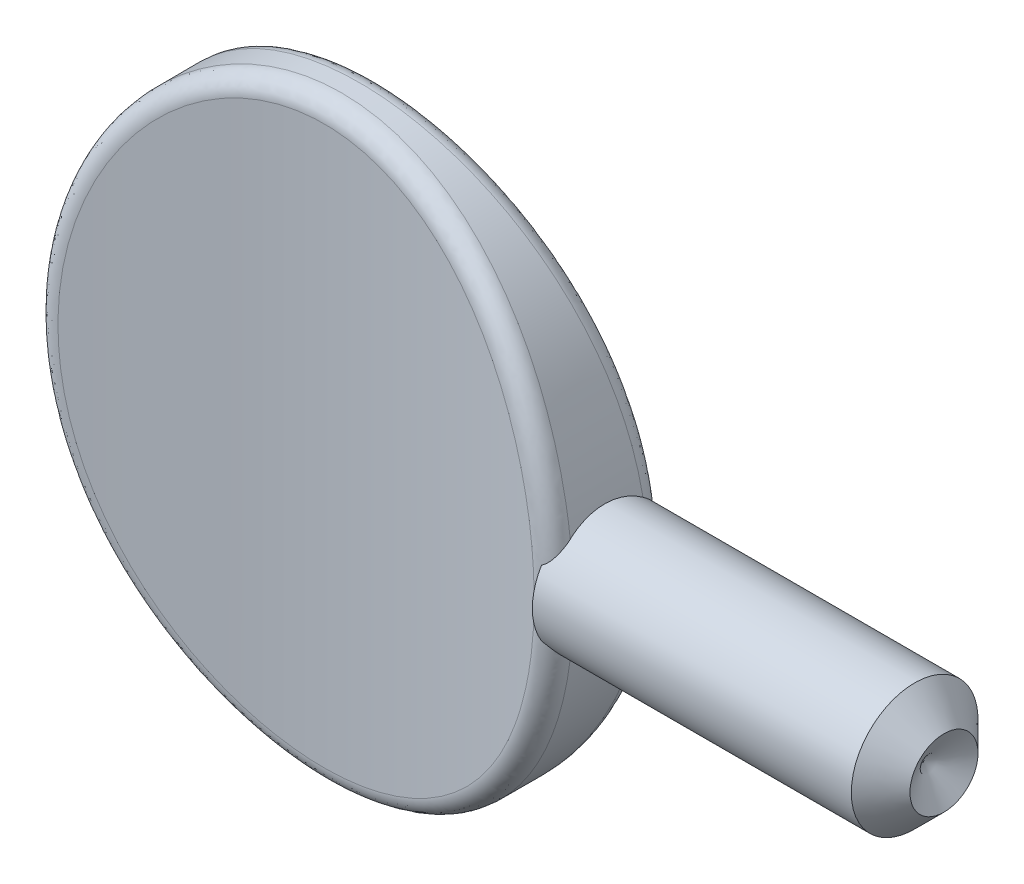
SolidWorks part; units mm, degrees
ref_plane "Front" through (0, 0, 0) normal (0, 0, 1) x (1, 0, 0)
ref_plane "Top" through (0, 0, 0) normal (0, 1, 0) x (1, 0, 0)
ref_plane "Right" through (0, 0, 0) normal (1, 0, 0) x (0, 0, -1)
ref_axis "Axis1" through (-50, 0, 0) along (1, 0, 0)
sketch "Sketch1" plane through (0, 0, 0) normal (0, 0, 1) x (1, 0, 0)
  line L0 (0, 0) -> (22.606, 0) construction
  line L1 (13.208, -2.413) -> (13.208, 2.413)
  line L2 (13.208, -2.413) -> (9.6776, -2.413) construction
  ellipse E0 centre (0, 0) end of major axis (0, -11.303) minor radius 9.906
  dimension "D2" = 3.302
  dimension "B" = 19.812
  dimension "L" = 12.7
extrude "Extrude1" add sketch "Sketch1" along normal mid plane 4.572
sketch "Sketch2" plane through (0, 0, 0) normal (0, 1, 0) x (1, 0, 0)
  line L0 (9.906, 2.286) -> (-9.906, 2.286) construction
  line L1 (0, 0) -> (0, 1.1721) construction
  line L2 (-1.7991, 0) -> (2.0444, 0) construction
  line L3 (-9.906, -2.286) -> (9.906, -2.286) construction
  line L6 (-9.906, 2.286) -> (-9.906, -2.286)
  line L7 (9.906, 2.286) -> (9.906, -2.286)
  arc A0 (-9.906, 2.286) -> (9.906, 2.286) centre (0, 40.2844) ccw
  arc A1 (-9.906, -2.286) -> (9.906, -2.286) centre (0, -40.2844) cw
extrude "Cut-Extrude1" cut sketch "Sketch2" against normal through all and the other way through all flip side to cut
fillet "Fillet3" radius 0.6773 2 edges at (-9.9037, -0.2444, 2.2854) (0.1692, 11.3014, -1.0164)
sketch "Sketch3" plane through (0, 0, 0) normal (0, 1, 0) x (1, 0, 0)
  line L0 (21.4884, 2.413) -> (22.606, 1.2954)
  line L1 (0, 0) -> (21.0288, 0) construction
  line L2 (0, 0) -> (22.606, 0) construction
  line L3 (13.208, 2.413) -> (13.208, 0) construction
  line L4 (13.208, 2.413) -> (21.4884, 2.413)
  line L5 (22.606, 1.2954) -> (21.8276, 0)
  line L6 (13.208, 2.413) -> (9.3367, 2.413)
  line L7 (9.0722, 2.0783) -> (9.0722, 0)
  line L8 (9.3367, 0) -> (9.3367, 2.413) construction
  line L9 (9.0722, 0) -> (21.8276, 0)
  arc A0 (9.3367, 2.413) -> (9.0722, 2.0783) centre (8.9927, 2.413) cw
  arc A3 (-9.906, 2.286) -> (9.906, 2.286) centre (0, 40.2844) ccw construction
  dimension "D1" = 45
  dimension "D2" = 59
revolve "Revolve1" add sketch "Sketch3" angle 360 about L0
cosmetic thread "Cosmetic Thread1" [suppressed]
sketch "Sketch4" plane through (0, 0, 0) normal (0, 0, 1) x (1, 0, 0)
  line L0 (0, 0) -> (27.7993, 0) construction
  line L1 (21.3051, 2.413) -> (21.4884, 2.0955)
  line L2 (21.4884, 2.0955) -> (21.6717, 2.413)
  line L3 (21.6717, 2.413) -> (21.6717, 2.7796)
  line L4 (21.6717, 2.7796) -> (21.3051, 2.7796)
  line L5 (21.3051, 2.7796) -> (21.3051, 2.413)
  line L6 (21.4884, 2.413) -> (21.4884, -2.413) construction
  dimension "D1" = 4.191
  dimension "D2" = 4.826
revolve "Cut-Revolve10" [suppressed] cut sketch "Sketch4" angle 360 about L0
pattern_linear "LPattern10" [suppressed] count 23 along (-1, 0, 0) of bodies 109
equation "\"D2@Sketch1\" = \"B@Sketch1\" / 6"
equation "\"D1@Fillet3\" = \"C1@Sketch2\" / 3"
equation "\"DIA@Sketch3\" = \"D@Sketch1\""
equation "\"D1@Cosmetic Thread1\" = \"L@Sketch1\" -  ( \"D@Sketch1\" - \"cup_dia@Sketch3\" )  / 2"
equation "\"D1@Sketch4\" = \"D2@Cosmetic Thread1\""
equation "\"D2@Sketch4\" = \"DIA@Sketch3\""
equation "\"D1@LPattern10\" = \"D1@Cosmetic Thread1\" / \"P@LPattern10\" "
